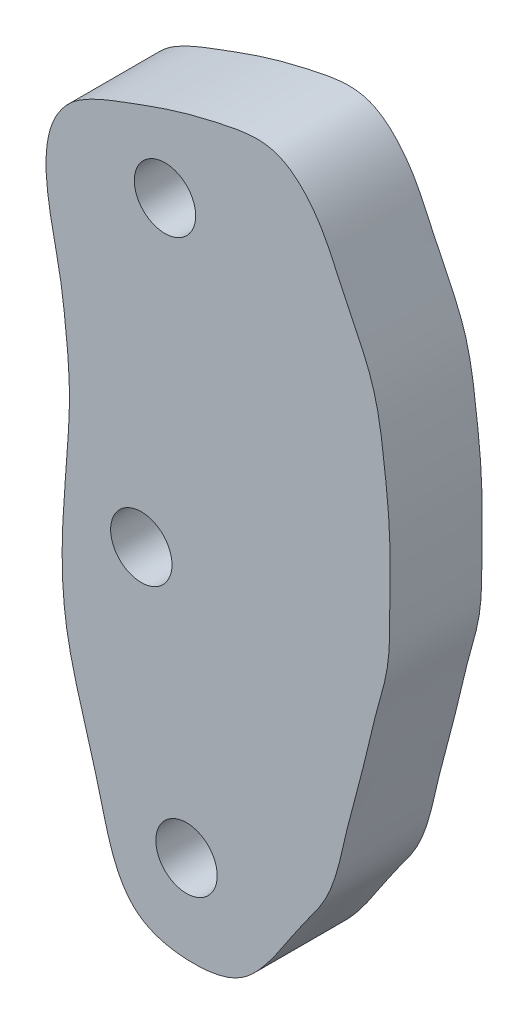
SolidWorks part; units mm, degrees
ref_plane "Спереди" through (0, 0, 0) normal (0, 0, 1) x (1, 0, 0)
ref_plane "Сверху" through (0, 0, 0) normal (0, 1, 0) x (1, 0, 0)
ref_plane "Справа" through (0, 0, 0) normal (1, 0, 0) x (0, 0, -1)
other "Configuration Table"
sketch "Sketch1" plane through (0, 0, 0) normal (0, 0, 1) x (1, 0, 0)
  spline S0 degree 3 poles (-12.2693, 28.0898) (-11.0911, 28.5313) (-9.6756, 29.0593) (-8.0628, 29.4573) (-6.3432, 29.7677) (-4.8854, 28.43) (-4.1667, 26.5835) (-3.0811, 24.6299) (-2.8058, 22.4777) (-2.595, 20.5722) (-2.6529, 18.668) (-2.5864, 16.9351) (-3.1669, 15.0861) (-3.533, 13.326) (-4.1246, 11.3106) (-4.4423, 9.4697) (-5.624, 7.9939) (-6.406, 6.6831) (-7.5094, 5.431) (-9.1128, 5.1764) (-11.4479, 5.5882) (-11.9822, 8.3133) (-12.6816, 10.6004) (-13.289, 12.833) (-13.3569, 15.3838) (-13.1344, 17.5852) (-13.039, 19.5899) (-13.1758, 20.9962) (-13.3976, 22.8542) (-13.9059, 24.6333) (-13.8361, 26.5453) (-13.1021, 27.587) (-12.2693, 28.0898) (-11.0911, 28.5313) (-9.6756, 29.0593) knots -0.048508 -0.034435 -0.019036 0 0.029558 0.05704 0.08595 0.111532 0.148878 0.187113 0.223386 0.257681 0.28442 0.320102 0.344602 0.382071 0.411256 0.451666 0.474121 0.505641 0.530331 0.554661 0.585285 0.639531 0.673538 0.711102 0.755328 0.802268 0.823407 0.857005 0.873817 0.918175 0.951492 0.965565 0.980964 1 1.029558 1.05704 1.08595 only from (-11.2834, 28.459) to (-11.2834, 28.459)
  point P2 (-13.1726, 12.7138)
  point P4 (-12.6568, 10.5535)
  point P5 (-12.1086, 8.619)
  point P6 (-13.3016, 15.3254)
extrude "Boss-Extrude1" add sketch "Sketch1" along normal blind 3
ref_plane "Plane1" through (0, 0, 3) normal (0, 0, 1) x (1, 0, 0)
sketch "Sketch2" plane through (0, 0, 3) normal (0, 0, 1) x (1, 0, 0)
  circle A0 centre (-10.7321, 16.1742) radius 1
  circle A1 centre (-9.9601, 26.414) radius 1
  circle A2 centre (-9.2585, 8.1323) radius 1
  point P2 (-9.8471, 16.6434)
  point P3 (-9.8471, 16.6434)
  point P4 (-10.7321, 16.1742)
  point P5 (0, 0)
  point P8 (-6.3295, 25.109)
  point P9 (-10.4572, 27.9145)
  point P10 (0, 0)
  point P13 (-7.4548, 4.594)
  point P14 (-9.9601, 26.414)
  point P15 (-9.2585, 8.1323)
  dimension "D1" = 2
extrude "Cut-Extrude1" cut sketch "Sketch2" against normal up to surface (3 mm away) contours A1 | A2 | A0 region at (-9.9601, 26.414, 3) region at (-9.2585, 8.1323, 3)
equation "\"R small\"= 2"
equation "\"R big\"= 4"
equation "\"width\"= 0.6"
equation "\"border width\"= 1"
equation "\"thickness\"= 3"
equation "\"D1@Boss-Extrude1\"=\"thickness\""
equation "\"D1@Sketch2\"=\"R small\""
